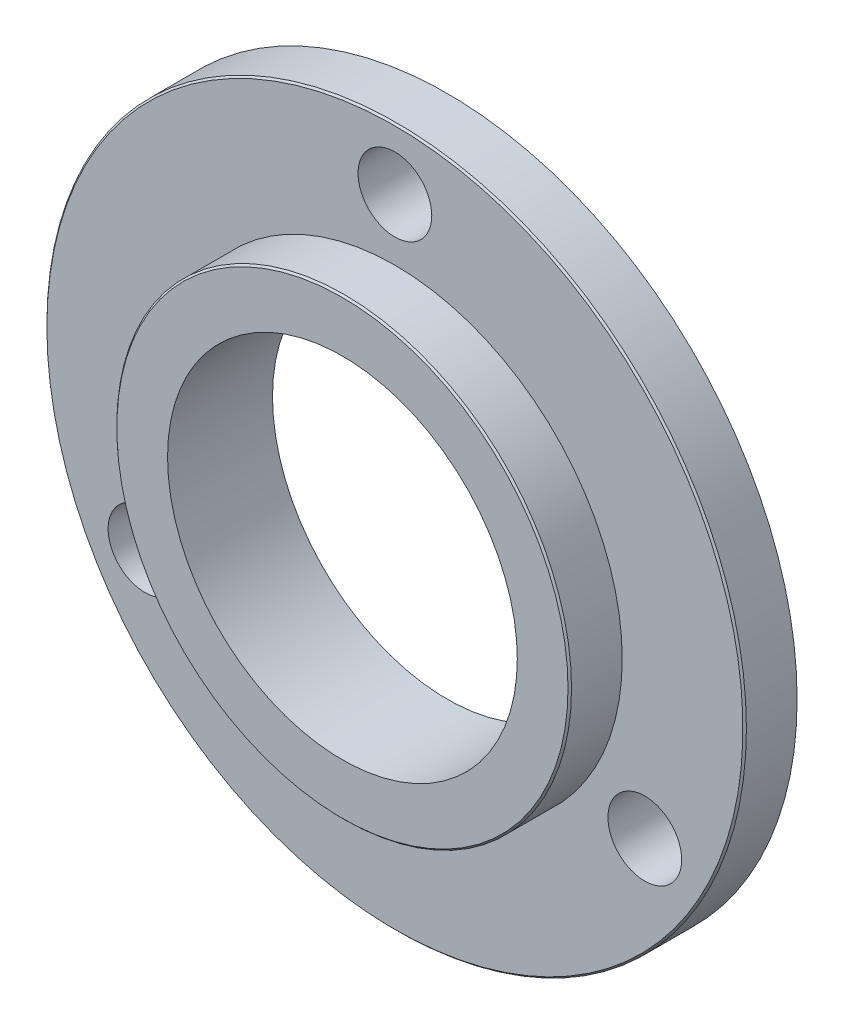
SolidWorks part; units mm, degrees
ref_plane "Plan de face" through (0, 0, 0) normal (0, 0, 1) x (1, 0, 0)
ref_plane "Plan de dessus" through (0, 0, 0) normal (0, 1, 0) x (1, 0, 0)
ref_plane "Plan de droite" through (0, 0, 0) normal (1, 0, 0) x (0, 0, -1)
sketch "Esquisse1" [suppressed] plane through (0, 0, 0) normal (0, 0, 1) x (1, 0, 0)
  circle A0 centre (0, 0) radius 40.8746
sketch "Esquisse10" plane through (0, 0, 0) normal (0, 0, 1) x (1, 0, 0)
  circle A0 centre (0, 0) radius 13
  circle A1 centre (0, 0) radius 10
extrude "Boss.-Extru.2" add sketch "Esquisse10" along normal blind 3
sketch "Esquisse11" plane through (0, 0, 0) normal (0, 0, -1) x (-1, 0, 0)
  circle A0 centre (0, 0) radius 10
  circle A1 centre (0, 0) radius 20
extrude "Boss.-Extru.3" add sketch "Esquisse11" along normal blind 3
sketch "Sketch4" plane through (0, 0, 0) normal (0, 0, 1) x (1, 0, 0)
  line L0 (0, 20) -> (0, 13)
  circle A0 centre (0, 0) radius 20 construction
  circle A1 centre (0, 0) radius 13 construction
hole_wizard "Hole for #4 300® SC Nuts (SP)1" positions "Sketch5" profile "Sketch6" hole size "#4-40" standard "PEM® Inch"
sketch "Sketch5" plane through (0, 0, 0) normal (0, 0, 1) x (1, 0, 0)
  line L0 (0, 20) -> (0, 13) construction
  point P0 (0, 16.5)
sketch "Sketch6" plane through (0, 16.5, 0) normal (1, 0, 0) x (0, -1, 0)
  line L0 (0, 0) -> (0, 6.2667)
  line L1 (0, 6.2667) -> (2.1082, 5)
  line L2 (2.1082, 5) -> (2.1082, 0)
  line L5 (2.1082, 0) -> (0, 0)
  line L10 (0, 6.2667) -> (-2.1082, 5) construction
  line L11 (0, -6.35) -> (0, 107.95) construction
  dimension "Hole Dia." = 4.2164
  dimension "Hole Depth" = 5
  dimension "Drill Angle" = 118
pattern_circular "CirPattern1" count 3 over 360 about axis through (0, 0, 3) along (0, 0, -1) of "Hole for #4 300® SC Nuts (SP)1"
chamfer "Chamfer1" distance 0.1 angle 45 1 edges at (-20, 0, 0)
chamfer "Chamfer2" distance 0.1 angle 45 1 edges at (13, 0, 3)
